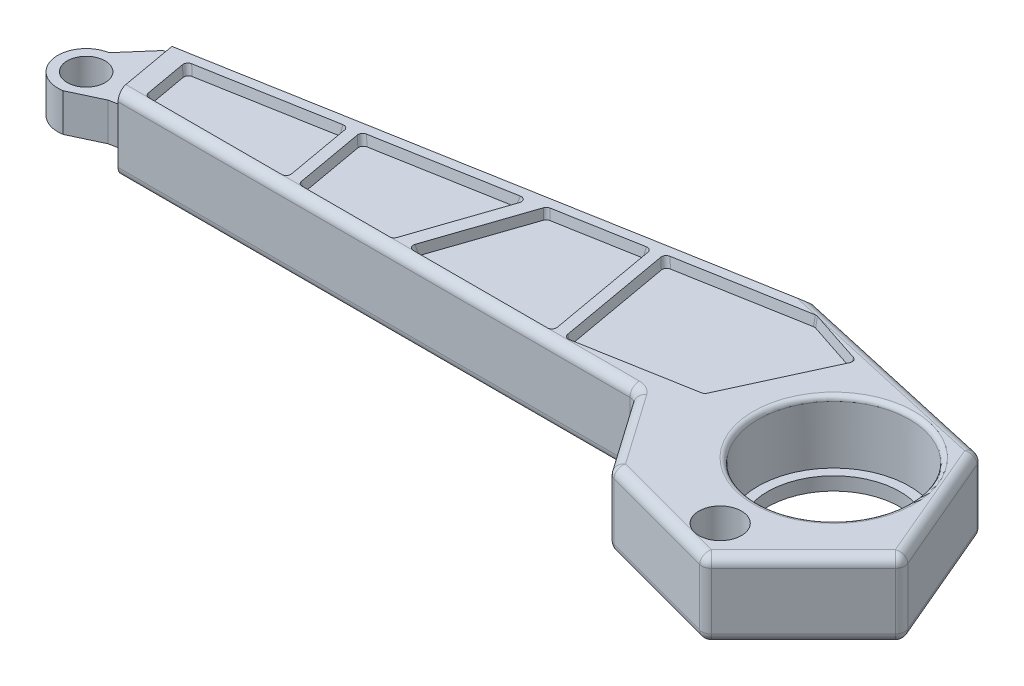
SolidWorks part; units mm, degrees
material "201 Annealed Stainless Steel (SS)"
ref_plane "Front Plane" through (0, 0, 0) normal (0, 0, 1) x (1, 0, 0)
ref_plane "Top Plane" through (0, 0, 0) normal (0, 1, 0) x (1, 0, 0)
ref_plane "Right Plane" through (0, 0, 0) normal (1, 0, 0) x (0, 0, -1)
sketch "Sketch3" plane through (0, 0, 0) normal (0, 1, 0) x (1, 0, 0)
  line L0 (0, 0) -> (60, 0)
  line L1 (0, 0) -> (-1.2941, -4.8296)
  line L2 (0, 0) -> (0, -4.8377) construction
  line L3 (-1.2941, -4.8296) -> (-15.783, -0.9473)
  line L4 (-15.783, -0.9473) -> (-13.7124, 6.7801)
  line L5 (60, 0) -> (65.7358, -8.1915)
  line L6 (60, 0) -> (60, -12.4774) construction
  line L7 (65.7358, -8.1915) -> (79.0223, -11.7516)
  line L8 (65.7358, -8.1915) -> (69.8229, -5.3297) construction
  line L9 (79.0223, -11.7516) -> (89.6289, -1.145)
  line L10 (79.0223, -11.7516) -> (79.9762, -8.1915) construction
  line L11 (89.6289, -1.145) -> (83.7679, 12.6625)
  line L12 (83.7679, 12.6625) -> (55.2001, 19.0711)
  line L13 (55.2001, 19.0711) -> (-13.7124, 6.7801)
  line L14 (89.6289, -1.145) -> (84.3256, 4.1583) construction
  dimension "D1" = 60
  dimension "D2" = 5
  dimension "D3" = 15
  dimension "D4" = 15
  dimension "D5" = 35
  dimension "D6" = 10
  dimension "D7" = 50
  dimension "D8" = 30
  dimension "D9" = 15
  dimension "D10" = 22
  dimension "D11" = 15
  dimension "D12" = 8
  dimension "D13" = 70
  dimension "D14" = 29.2779
extrude "Boss-Extrude1" add sketch "Sketch3" along normal blind 8
sketch "Sketch4" plane through (0, 8, 0) normal (0, 1, 0) x (1, 0, 0)
  line L0 (79.0223, -11.7516) -> (79.0223, -7.7516) construction
  line L1 (79.0223, -7.7516) -> (76.7723, -7.7516) construction
  circle A0 centre (76.7723, -7.7516) radius 2.25
  dimension "D1" = 4
  dimension "D2" = 2.25
extrude "Cut-Extrude1" cut sketch "Sketch4" against normal through all
fillet "Fillet1" radius 1 3 edges at (83.7679, 4, -12.6625) (79.0223, 4, 11.7516) (89.6289, 4, 1.145)
fillet "Fillet2" radius 1 3 edges at (0, 4, 0) (60, 4, 0) (65.7358, 4, 8.1915)
fillet "Fillet4" radius 1 1 edges at (-13.7124, 4, -6.7801)
sketch "Sketch9" plane through (-1.2941, 0, 4.8296) normal (-0.2588, 0, 0.9659) x (0.9659, 0, 0.2588)
  line L0 (-15, 8) -> (-14, 8) construction
  line L1 (-15, 8) -> (0, 8) construction
  line L2 (-15, 0) -> (0, 0) construction
  line L3 (-14, 8) -> (-13, 8)
  line L4 (-14, 8) -> (-14, 0)
  line L5 (-14, 0) -> (-13, 0)
  line L6 (-13, 8) -> (-13, 0)
  line L8 (-12, 0) -> (-11, 0)
  line L9 (-12, 0) -> (-12, 8)
  line L10 (-12, 8) -> (-11, 8)
  line L11 (-11, 0) -> (-11, 8)
  line L12 (-10, 8) -> (-9, 8)
  line L13 (-10, 8) -> (-10, 0)
  line L14 (-10, 0) -> (-9, 0)
  line L15 (-9, 8) -> (-9, 0)
  line L20 (-6, 8) -> (-5, 8)
  line L21 (-6, 8) -> (-6, 0)
  line L22 (-6, 0) -> (-5, 0)
  line L23 (-5, 8) -> (-5, 0)
  line L24 (-4, 8) -> (-3, 8)
  line L25 (-4, 8) -> (-4, 0)
  line L26 (-4, 0) -> (-3, 0)
  line L27 (-3, 8) -> (-3, 0)
  line L28 (-2, 8) -> (-1, 8)
  line L29 (-2, 8) -> (-2, 0)
  line L30 (-2, 0) -> (-1, 0)
  line L31 (-1, 8) -> (-1, 0)
  line L32 (-8, 8) -> (-7, 8)
  line L33 (-8, 8) -> (-8, 0)
  line L34 (-8, 0) -> (-7, 0)
  line L35 (-7, 8) -> (-7, 0)
  dimension "D1" = 1
  dimension "D2" = 1
  dimension "D3" = 1
  dimension "D4" = 1
  dimension "D5" = 1
  dimension "D6" = 1
  dimension "D7" = 1
  dimension "D8" = 1
  dimension "D9" = 1
  dimension "D10" = 1
  dimension "D11" = 1
  dimension "D12" = 1
  dimension "D13" = 1
  dimension "D14" = 1
extrude "Cut-Extrude5" cut sketch "Sketch9" against normal blind 0.3
sketch "Sketch10" plane through (0, 8, 0) normal (0, 1, 0) x (1, 0, 0)
  line L0 (55.2001, 19.0711) -> (-13.0866, 6.8917) construction
  line L1 (3.6493, 9.8766) -> (5.4108, 0)
  line L2 (0.7673, 0) -> (59.4794, 0) construction
  line L3 (3.6493, 9.8766) -> (-17.4488, 6.1136)
  line L4 (-17.4488, 6.1136) -> (-13.9885, -10.791)
  line L5 (-13.9885, -10.791) -> (6.5844, -6.5798)
  line L6 (6.5844, -6.5798) -> (5.4108, 0)
  dimension "D1" = 17
extrude "Cut-Extrude6" cut sketch "Sketch10" against normal through all
sketch "Sketch11" plane through (5.244, 0, -0.9353) normal (-0.9845, 0, 0.1756) x (0.1756, 0, 0.9845)
  line L0 (-9.0824, 0) -> (-9.0824, 8) construction
  line L1 (-9.0824, 6) -> (0.9501, 6)
  line L2 (-9.0824, 6) -> (-9.0824, 2)
  line L3 (-9.0824, 2) -> (0.9501, 2)
  line L4 (0.9501, 6) -> (0.9501, 2)
  line L5 (0.9501, 8) -> (0.9501, 0) construction
  line L6 (0.9501, 8) -> (-9.0824, 8) construction
  line L7 (0.9501, 0) -> (-9.0824, 0) construction
  dimension "D1" = 2
  dimension "D2" = 2
extrude "Boss-Extrude2" add sketch "Sketch11" along normal blind 5
sketch "Sketch12" plane through (0, 6, 0) normal (0, 1, 0) x (1, 0, 0)
  line L0 (0.4885, -0.8779) -> (-0.0382, 2.0755) construction
  line L1 (0.4885, -0.8779) -> (-1.273, 8.9987) construction
  circle A0 centre (-0.0382, 2.0755) radius 3
  dimension "D1" = 3
extrude "Boss-Extrude3" add sketch "Sketch12" against normal blind 4
sketch "Sketch13" plane through (0, 6, 0) normal (0, 1, 0) x (1, 0, 0)
  circle A0 centre (-0.0382, 2.0755) radius 2
extrude "Cut-Extrude7" cut sketch "Sketch13" against normal through all
sketch "Sketch14" plane through (5.244, 0, -0.9353) normal (-0.9845, 0, 0.1756) x (0.1756, 0, 0.9845)
  line L0 (-9.0824, 6) -> (-9.0824, 8) construction
  line L1 (-9.0824, 7) -> (-7.7824, 7) construction
  circle A0 centre (-7.7824, 7) radius 0.5
  dimension "D1" = 1.3
extrude "Cut-Extrude8" cut sketch "Sketch14" against normal blind 2
sketch "Sketch15" plane through (0, 6, 0) normal (0, 1, 0) x (1, 0, 0)
  line L0 (-0.565, 5.0289) -> (3.6493, 9.8766)
  line L1 (3.6493, 9.8766) -> (-1.273, 8.9987)
  line L2 (-1.273, 8.9987) -> (-0.565, 5.0289)
extrude "Cut-Extrude9" cut sketch "Sketch15" against normal through all
sketch "Sketch16" plane through (0, 6, 0) normal (0, 1, 0) x (1, 0, 0)
  line L0 (0.4885, -0.8779) -> (5.1756, 1.3189)
  line L1 (5.4108, 0) -> (3.6493, 9.8766) construction
  line L2 (5.1756, 1.3189) -> (5.4108, 0)
  line L3 (5.4108, 0) -> (0.4885, -0.8779)
  dimension "D1" = 15
extrude "Cut-Extrude10" cut sketch "Sketch16" against normal through all
sketch "Sketch17" plane through (0, 6, 0) normal (0, 1, 0) x (1, 0, 0)
  line L0 (5.1756, 1.3189) -> (3.6493, 9.8766) construction
  line L1 (3.6493, 9.8766) -> (3.9126, 8.3999) construction
  line L2 (3.9126, 8.3999) -> (2.0817, 8.0734)
  line L3 (-0.565, 5.0289) -> (3.6493, 9.8766) construction
  line L4 (2.0817, 8.0734) -> (3.6493, 9.8766)
  line L5 (3.6493, 9.8766) -> (3.9126, 8.3999)
  dimension "D1" = 1.5
extrude "Cut-Extrude12" cut sketch "Sketch17" against normal through all
sketch "Sketch19" plane through (0, 6, 0) normal (0, 1, 0) x (1, 0, 0)
  line L0 (5.2436, 0.9375) -> (3.7217, 0.6375)
  line L1 (5.4108, 0) -> (3.6493, 9.8766) construction
  line L2 (5.1756, 1.3189) -> (0.4885, -0.8779) construction
  line L3 (3.7217, 0.6375) -> (5.1756, 1.3189)
  line L4 (5.1756, 1.3189) -> (5.2436, 0.9375)
extrude "Boss-Extrude4" add sketch "Sketch19" against normal blind 4
sketch "Sketch20" plane through (0, 2, 0) normal (0, -1, 0) x (1, 0, 0)
  circle A0 centre (-0.0382, -2.0755) radius 1.5
  circle A1 centre (-0.0382, -2.0755) radius 2
  dimension "D1" = 3
extrude "Boss-Extrude5" add sketch "Sketch20" against normal blind 1
sketch "Sketch21" plane through (0, 8, 0) normal (0, 1, 0) x (1, 0, 0)
  line L0 (76.7723, -7.7516) -> (76.7723, 4.2484) construction
  circle A0 centre (76.7723, 4.2484) radius 8
  dimension "D2" = 16
  dimension "D1" = 12
extrude "Cut-Extrude13" cut sketch "Sketch21" against normal blind 6.6
sketch "Sketch22" plane through (0, 1.4, 0) normal (0, 1, 0) x (1, 0, 0)
  circle A0 centre (76.7723, 4.2484) radius 7
  dimension "D1" = 14
extrude "Cut-Extrude14" cut sketch "Sketch22" against normal through all
fillet "Fillet5" radius 0.5 1 edges at (76.7723, 8, 3.7516)
chamfer "Chamfer1" distance 3 angle 45 2 edges at (29.4247, 0, -14.4739) (29.4247, 8, -14.4739)
sketch "Sketch23" plane through (0, 8, 0) normal (0, 1, 0) x (1, 0, 0)
  line L0 (6.3205, 6.29) -> (7.264, 1)
  line L1 (7.264, 1) -> (22.264, 1)
  line L2 (22.264, 1) -> (20.8581, 8.8828)
  line L3 (20.8581, 8.8828) -> (6.3205, 6.29)
  line L4 (62.7676, 17.3735) -> (4.176, 6.9233) construction
  line L5 (5.4108, 0) -> (4.176, 6.9233) construction
  line L6 (5.4108, 0) -> (59.4794, 0) construction
  line L7 (5.2436, 0.9375) -> (3.9126, 8.3999) construction
  dimension "D1" = 15
  dimension "D2" = 1
  dimension "D3" = 1
  dimension "D4" = 2
extrude "Cut-Extrude15" cut sketch "Sketch23" against normal blind 1
sketch "Sketch26" plane through (0, 0, 0) normal (0, -1, 0) x (1, 0, 0)
  line L0 (7.264, -1) -> (22.264, -1)
  line L1 (22.264, -1) -> (20.8581, -8.8828)
  line L2 (20.8581, -8.8828) -> (6.3205, -6.29)
  line L3 (6.3205, -6.29) -> (7.264, -1)
extrude "Cut-Extrude18" cut sketch "Sketch26" against normal blind 1
chamfer "Chamfer3" distance 1 angle 10 4 edges at (21.5611, 7, -4.9414) (14.764, 7, -1) (6.7923, 7, -3.645) (13.5893, 7, -7.5864) first distance on face at (21.5611, 7.5, -4.9414) first distance on face at (14.764, 7.5, -1) first distance on face at (6.7923, 7.5, -3.645) first distance on face at (13.5893, 7.5, -7.5864)
fillet "Fillet6" radius 0.5 4 edges at (22.1588, 7.5, -1.0882) (7.3379, 7.5, -1.0882) (6.4228, 7.5, -6.2186) (20.7868, 7.5, -8.7806)
sketch "Sketch24" plane through (0, 8, 0) normal (0, 1, 0) x (1, 0, 0)
  line L0 (17.4591, 8.2766) -> (62.8491, 16.3722) construction
  line L1 (20.3733, 8.7964) -> (6.8053, 6.3764) construction
  line L2 (15.7859, 1) -> (62.8491, 1) construction
  line L3 (7.6764, 1) -> (21.676, 1) construction
  line L4 (62.8491, 1) -> (62.8491, 16.3722) construction
  line L5 (21.9954, 9.0857) -> (23.4375, 1)
  line L6 (23.4375, 1) -> (33.4375, 1)
  line L7 (33.4375, 1) -> (37.0976, 11.7793)
  line L8 (37.0976, 11.7793) -> (21.9954, 9.0857)
  line L9 (38.6611, 12.0581) -> (34.9063, 1)
  line L10 (34.9063, 1) -> (50.3368, 1)
  line L11 (50.3368, 1) -> (48.0654, 13.7354)
  line L12 (48.0654, 13.7354) -> (38.6611, 12.0581)
  line L13 (49.2011, 13.938) -> (51.5087, 1)
  line L15 (64.0842, 3.2429) -> (69.1527, 14.2941)
  line L16 (69.1527, 14.2941) -> (62.8491, 16.3722)
  line L17 (62.8491, 16.3722) -> (49.2011, 13.938)
  line L18 (51.5087, 1) -> (64.0842, 3.2429)
  dimension "D1" = 10
  dimension "D2" = 9.5527
extrude "Cut-Extrude16" cut sketch "Sketch24" against normal blind 1 contours L8 L5 L6 L7 | L12 L9 L10 L11 | L15 L16 L17 L13 L18
sketch "Sketch25" plane through (0, 0, 0) normal (0, -1, 0) x (1, 0, 0)
  line L0 (23.4375, -1) -> (21.9954, -9.0857)
  line L1 (21.9954, -9.0857) -> (37.0976, -11.7793)
  line L2 (37.0976, -11.7793) -> (33.4375, -1)
  line L3 (33.4375, -1) -> (23.4375, -1)
  line L4 (34.9063, -1) -> (38.6611, -12.0581)
  line L5 (38.6611, -12.0581) -> (48.0654, -13.7354)
  line L6 (48.0654, -13.7354) -> (50.3368, -1)
  line L7 (50.3368, -1) -> (34.9063, -1)
  line L8 (51.5087, -1) -> (49.2011, -13.938)
  line L9 (49.2011, -13.938) -> (62.8491, -16.3722)
  line L10 (62.8491, -16.3722) -> (69.1527, -14.2941)
  line L11 (69.1527, -14.2941) -> (64.0842, -3.2429)
  line L12 (64.0842, -3.2429) -> (51.5087, -1)
extrude "Cut-Extrude17" cut sketch "Sketch25" against normal blind 1
chamfer "Chamfer4" distance 1 angle 10 26 edges at (35.2675, 1, -6.3896) (29.5465, 1, -10.4325) (22.7164, 1, -5.0428) (28.4375, 1, -1) (49.2011, 1, -7.3677) (43.3632, 1, -12.8968) (36.7837, 1, -6.5291) (42.6216, 1, -1) (66.6185, 1, -8.7685) (66.0009, 1, -15.3332) (56.0251, 1, -15.1551) (50.3549, 1, -7.469) (57.7965, 1, -2.1215) (50.3549, 7, -7.469) (56.0251, 7, -15.1551) (66.0009, 7, -15.3332) (66.6185, 7, -8.7685) (57.7965, 7, -2.1215) (42.6216, 7, -1) (36.7837, 7, -6.5291) (43.3632, 7, -12.8968) (49.2011, 7, -7.3677) (28.4375, 7, -1) (22.7164, 7, -5.0428) (29.5465, 7, -10.4325) (35.2675, 7, -6.3896) first distance on face at (35.2675, 0.5, -6.3896) first distance on face at (29.5465, 0.5, -10.4325) first distance on face at (22.7164, 0.5, -5.0428) first distance on face at (28.4375, 0.5, -1) first distance on face at (49.2011, 0.5, -7.3677) first distance on face at (43.3632, 0.5, -12.8968) first distance on face at (36.7837, 0.5, -6.5291) first distance on face at (42.6216, 0.5, -1) first distance on face at (66.6185, 0.5, -8.7685) first distance on face at (66.0009, 0.5, -15.3332) first distance on face at (56.0251, 0.5, -15.1551) first distance on face at (50.3549, 0.5, -7.469) first distance on face at (57.7965, 0.5, -2.1215) first distance on face at (50.3549, 7.5, -7.469) first distance on face at (56.0251, 7.5, -15.1551) first distance on face at (66.0009, 7.5, -15.3332) first distance on face at (66.6185, 7.5, -8.7685) first distance on face at (57.7965, 7.5, -2.1215) first distance on face at (42.6216, 7.5, -1) first distance on face at (36.7837, 7.5, -6.5291) first distance on face at (43.3632, 7.5, -12.8968) first distance on face at (49.2011, 7.5, -7.3677) first distance on face at (28.4375, 7.5, -1) first distance on face at (22.7164, 7.5, -5.0428) first distance on face at (29.5465, 7.5, -10.4325) first distance on face at (35.2675, 7.5, -6.3896)
fillet "Fillet7" radius 0.5 30 edges at (64.0233, 0.5, -3.3216) (69.0315, 0.5, -14.2412) (62.8427, 0.5, -16.2815) (49.3034, 0.5, -13.8667) (51.58, 0.5, -1.1023) (35.0294, 0.5, -1.0882) (38.7278, 0.5, -11.9805) (47.9941, 0.5, -13.6332) (50.2316, 0.5, -1.0882) (22.264, 0.5, -1) (20.8581, 0.5, -8.8828) (6.3205, 0.5, -6.29) (7.264, 0.5, -1) (23.5113, 0.5, -1.0882) (22.0976, 0.5, -9.0144) (36.9661, 0.5, -11.6663) (33.3743, 0.5, -1.0882) (69.0315, 7.5, -14.2412) (62.8427, 7.5, -16.2815) (64.0233, 7.5, -3.3216) (51.58, 7.5, -1.1023) (49.3034, 7.5, -13.8667) (38.7278, 7.5, -11.9805) (47.9941, 7.5, -13.6332) (50.2316, 7.5, -1.0882) (35.0294, 7.5, -1.0882) (36.9661, 7.5, -11.6663) (33.3743, 7.5, -1.0882) (22.0976, 7.5, -9.0144) (23.5113, 7.5, -1.0882)
fillet "Fillet8" radius 1 22 edges at (73.0173, 8, -15.0742) (83.6885, 8, -12.5672) (86.667, 8, -5.8329) (89.4265, 8, 1.1057) (84.2913, 8, 6.4827) (78.9823, 8, 11.6022) (72.276, 8, 9.944) (65.7726, 8, 8.1389) (62.9128, 8, 4.1599) (59.9412, 8, 0.113) (73.0173, 0, -15.0742) (83.6885, 0, -12.5672) (86.667, 0, -5.8329) (89.4265, 0, 1.1057) (84.2913, 0, 6.4827) (78.9823, 0, 11.6022) (72.276, 0, 9.944) (65.7726, 0, 8.1389) (62.9128, 0, 4.1599) (59.9412, 0, 0.113) (32.4451, 8, 0) (32.4451, 0, 0)
